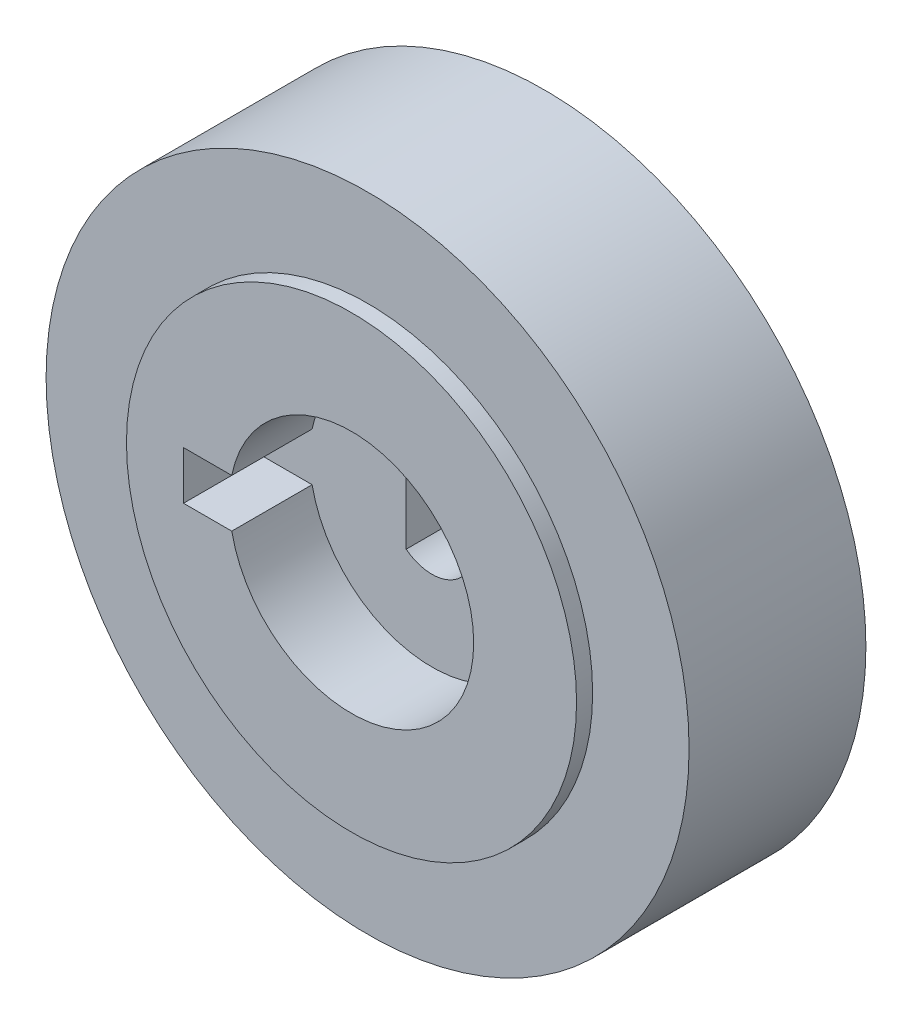
SolidWorks part; units mm, degrees
ref_plane "前视基准面" through (0, 0, 0) normal (0, 0, 1) x (1, 0, 0)
ref_plane "上视基准面" through (0, 0, 0) normal (0, 1, 0) x (1, 0, 0)
ref_plane "右视基准面" through (0, 0, 0) normal (1, 0, 0) x (0, 0, -1)
other "Configuration Table"
sketch "草图1" plane through (0, 0, 0) normal (0, 0, 1) x (1, 0, 0)
  line L0 (-1.6, 2.0494) -> (-1.6, -2.0494)
  circle A0 centre (0, 0) radius 2.6
  circle A1 centre (0, 0) radius 13
  circle A2 centre (0, 0) radius 1.4
  circle A3 centre (0, 0) radius 14
  dimension "D1" = 5.2
  dimension "D2" = 26
  dimension "D4" = 2.8
  dimension "D5" = 28
  dimension "D3" = 1.6
extrude "凸台-拉伸1" add sketch "草图1" along normal blind 4 contours A1 A0 | L0 A0 | L0 A0 A2 region at (1.1109, 2.2766, 0) region at (-2.0074, 0, 0) region at (-12.6323, 0, 0)
extrude "凸台-拉伸2" add sketch "草图1<3>" along normal blind 12 contours A1 A0 | L0 A0 region at (-2.0074, 0, 0) region at (-12.6323, 0, 0)
sketch "草图1<3>" plane through (0, 0, 0) normal (0, 0, 1) x (1, 0, 0) same geometry as "草图1"
extrude "凸台-拉伸3" add sketch "草图1<6>" along normal blind 1 from offset 11 contours A3 A1 region at (-13.604, 0, 0)
sketch "草图1<6>" plane through (0, 0, 0) normal (0, 0, 1) x (1, 0, 0) same geometry as "草图1"
sketch "草图3" plane through (0, 0, 0) normal (0, 0, -1) x (-1, 0, 0)
  line L0 (3.5554, -2.9187) -> (10.8646, -7.1387)
  line L1 (0.75, 4.5384) -> (-0.75, 4.5384)
  line L2 (0.75, 4.5384) -> (0.75, 12.9783)
  line L3 (0.75, 12.9783) -> (-0.75, 12.9783)
  line L4 (-0.75, 4.5384) -> (-0.75, 12.9783)
  line L5 (3.5554, -2.9187) -> (4.3054, -1.6197)
  line L6 (4.3054, -1.6197) -> (11.6146, -5.8397)
  line L7 (10.8646, -7.1387) -> (11.6146, -5.8397)
  line L8 (-4.3054, -1.6197) -> (-11.6146, -5.8397)
  line L9 (-4.3054, -1.6197) -> (-3.5554, -2.9187)
  line L10 (-3.5554, -2.9187) -> (-10.8646, -7.1387)
  line L11 (-11.6146, -5.8397) -> (-10.8646, -7.1387)
  circle A0 centre (0, 0) radius 1.4 construction
  circle A1 centre (0, 0) radius 1.4
  circle A2 centre (0, 0) radius 13 construction
  circle A3 centre (0, 0) radius 13
  circle A4 centre (0, 0) radius 4.6
  circle A5 centre (0, 0) radius 12
  arc A6 (1.6, 2.0494) -> (1.6, -2.0494) centre (0, 0) ccw construction
  arc A7 (1.6, 2.0494) -> (1.6, -2.0494) centre (0, 0) ccw
  point P33 (0, 0)
  dimension "D1" = 2
  dimension "D3" = 1
  dimension "D2" = 1.5
  dimension "D4" = 3
extrude "切除-拉伸1" cut sketch "草图3" against normal offset from surface (5 mm away) 7 contours L4 A5 L8 A4 | L10 A5 L0 A4 | L6 A5 L2 A4 region at (0, -7.5884, 0) region at (-6.5718, 3.7942, 0) region at (6.5718, 3.7942, 0) up to face at (0.5, 0, 12)
sketch "草图5" plane through (0, 0, 0) normal (0, 0, -1) x (-1, 0, 0)
  circle A0 centre (0, 0) radius 5
  dimension "D1" = 10
sketch "草图6" plane through (0, 0, 12) normal (0, 0, 1) x (1, 0, 0)
  line L0 (0, 0) -> (0, 11.2036) construction
  line L1 (-7.4505, -1.5) -> (-7.4505, 1.5)
  line L2 (-7.4505, -1.5) -> (-10.4505, -1.5)
  line L3 (-10.4505, -1.5) -> (-10.4505, 1.5)
  line L4 (-7.4505, 1.5) -> (-10.4505, 1.5)
  circle A0 centre (0, 0) radius 7.6
  arc M7 (-1.6, 2.0494) -> (-1.6, -2.0494) centre (0, 0) cw
  line M8 (-1.6, -2.0494) -> (-1.6, 2.0494)
  dimension "D1" = 15.2
  dimension "D2" = 3
  dimension "D3" = 3
extrude "切除-拉伸5" cut sketch "草图6" against normal blind 5 contours A0 L4 L3 L2 | A0 L0 L1 M7 M8 | L0 A0 M7 | L1 A0
extrude "切除-拉伸6" cut sketch "草图5" against normal offset from surface (2 mm away) 2 up to face at (0.5, 0, 4)
fillet "圆角1" radius 12 3 edges at (0, 5, 0) (-4.3301, -2.5, 0) (4.3301, -2.5, 0)
sketch "草图7" plane through (0, 0, 11) normal (0, 0, -1) x (-1, 0, 0)
  circle A0 centre (0, 0) radius 20
  circle A1 centre (0, 0) radius 13 construction
  circle A2 centre (0, 0) radius 13
  dimension "D1" = 40
extrude "凸台-拉伸5" add sketch "草图7" along normal up to surface (11 mm away) up to face at (0, 0, 0)
